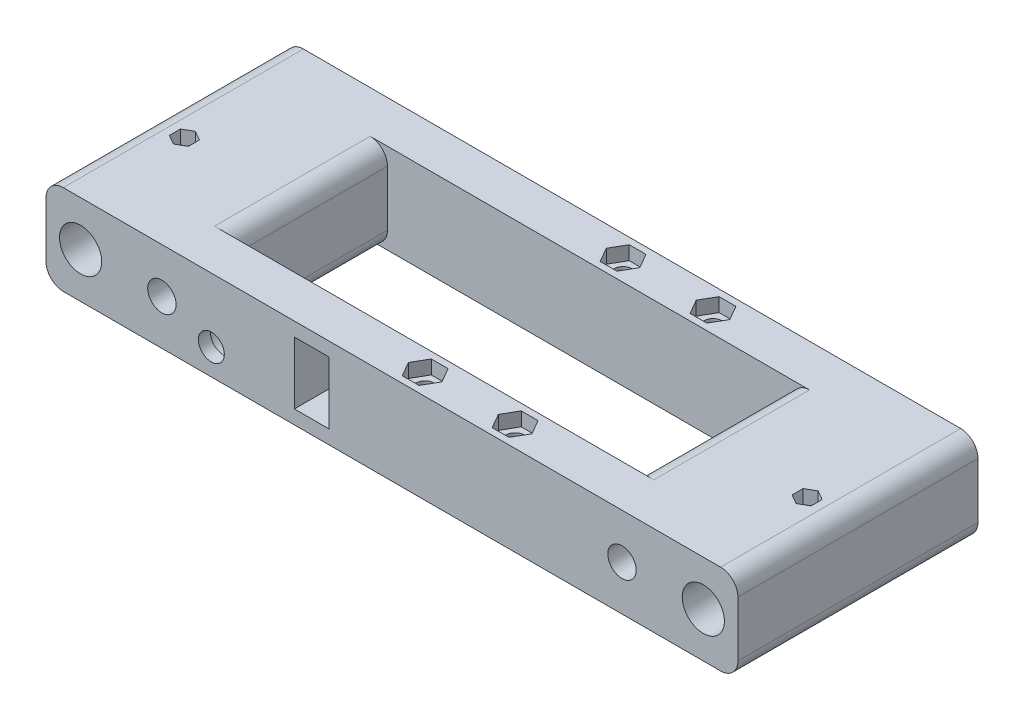
SolidWorks part; units mm, degrees
ref_plane "Front Plane" through (0, 0, 0) normal (0, 0, 1) x (1, 0, 0)
ref_plane "Top Plane" through (0, 0, 0) normal (0, 1, 0) x (1, 0, 0)
ref_plane "Right Plane" through (0, 0, 0) normal (1, 0, 0) x (0, 0, -1)
sketch "Sketch1" plane through (0, 0, 0) normal (0, 0, 1) x (1, 0, 0)
  line L0 (-58.5, 26) -> (-58.5, 0) construction
  line L1 (0, 0) -> (-100, 0)
  line L2 (0, 0) -> (0, 26)
  line L3 (0, 26) -> (-100, 26)
  line L4 (-100, 0) -> (-100, 26)
  circle A0 centre (-90, 13) radius 6.1
  circle A1 centre (-66.5, 13) radius 4.1
  point P9 (-100, 13)
  dimension "D3" = 12.2
  dimension "D4" = 8.2
  dimension "D1" = 100
  dimension "D2" = 26
  dimension "D5" = 23.5
  dimension "D6" = 10
  dimension "D7" = 8
  dimension "D8" = 41.5
extrude "Boss-Extrude1" add sketch "Sketch1" along normal blind 40
sketch "Sketch2" plane through (0, 0, 0) normal (0, 0, -1) x (-1, 0, 0)
  line L1 (100, 26) -> (0, 26)
  line L2 (100, 26) -> (100, 0)
  line L3 (100, 0) -> (0, 0)
  line L4 (0, 26) -> (0, 0)
extrude "Boss-Extrude2" add sketch "Sketch2" along normal blind 29.4
sketch "Sketch3" plane through (0, 26, 0) normal (0, 1, 0) x (1, 0, 0)
  line L0 (0, -40) -> (0, 29.4) construction
  line L1 (0, 17.2) -> (-58.5, 17.2)
  line L2 (0, 17.2) -> (0, -27.8)
  line L3 (0, -27.8) -> (-58.5, -27.8)
  line L4 (-58.5, 17.2) -> (-58.5, -27.8)
  line L5 (-100, -40) -> (-100, 29.4) construction
  line L6 (-100, 29.4) -> (0, 29.4) construction
  line L7 (0, -40) -> (-100, -40) construction
  dimension "D1" = 41.5
  dimension "D2" = 12.2
  dimension "D3" = 12.2
extrude "Cut-Extrude1" cut sketch "Sketch3" against normal up to next
mirror "Mirror2" about plane through (0, 0, 40) normal (-1, 0, 0) of "Boss-Extrude2", "Cut-Extrude1", "Boss-Extrude1"
sketch "Sketch4" plane through (0, 26, 0) normal (0, 1, 0) x (1, 0, 0)
  line L0 (-100, 29.4) -> (100, 29.4) construction
  line L1 (-5.5, 29.4) -> (-5.5, 17.2) construction
  line L2 (58.5, 17.2) -> (-58.5, 17.2) construction
  line L3 (58.5, 17.2) -> (58.5, -27.8) construction
  circle A0 centre (3.5, 23.3) radius 2.6
  circle A1 centre (29.5, 23.3) radius 2.6
  dimension "D1" = 6.1
  dimension "D3" = 9
  dimension "D4" = 26
  dimension "D5" = 5.2
  dimension "D2" = 64
extrude "Cut-Extrude2" cut sketch "Sketch4" against normal through all
sketch "Sketch5" plane through (0, 0, 0) normal (0, -1, 0) x (1, 0, 0)
  line L1 (34.2343, -23.3) -> (31.8671, -19.2)
  line L2 (31.8671, -19.2) -> (27.1329, -19.2)
  line L3 (27.1329, -19.2) -> (24.7657, -23.3)
  line L4 (24.7657, -23.3) -> (27.1329, -27.4)
  line L5 (27.1329, -27.4) -> (31.8671, -27.4)
  line L6 (31.8671, -27.4) -> (34.2343, -23.3)
  line L7 (-1.2343, -23.3) -> (1.1329, -27.4)
  line L8 (1.1329, -27.4) -> (5.8671, -27.4)
  line L9 (5.8671, -27.4) -> (8.2343, -23.3)
  line L10 (8.2343, -23.3) -> (5.8671, -19.2)
  line L11 (5.8671, -19.2) -> (1.1329, -19.2)
  line L12 (1.1329, -19.2) -> (-1.2343, -23.3)
  circle A0 centre (29.5, -23.3) radius 4.1 construction
  circle A1 centre (3.5, -23.3) radius 4.1 construction
  dimension "D1" = 8.2
  dimension "D2" = 8.2
extrude "Cut-Extrude3" cut sketch "Sketch5" against normal blind 4
ref_plane "Plane1" through (0, 0, 5.3) normal (0, 0, 1) x (1, 0, 0)
mirror "Mirror3" about plane through (0, 0, 5.3) normal (0, 0, 1) of "Cut-Extrude3", "Cut-Extrude2"
sketch "Sketch6" plane through (0, 0, 40) normal (0, 0, 1) x (1, 0, 0)
  line L0 (-8.1, 26) -> (-8.1, 0) construction
  line L1 (100, 26) -> (-100, 26) construction
  line L2 (-100, 0) -> (100, 0) construction
  line L3 (0.9, 26) -> (0.9, 4) construction
  line L4 (-100, 26) -> (-100, 0) construction
  line L5 (-18.2, 22) -> (-28.2, 22)
  line L6 (-18.2, 22) -> (-18.2, 4)
  line L7 (-18.2, 4) -> (-28.2, 4)
  line L8 (-28.2, 22) -> (-28.2, 4)
  point P12 (-28.2, 13)
  point P15 (-100, 13)
  dimension "D1" = 9
  dimension "D2" = 10.1
  dimension "D3" = 10
  dimension "D4" = 18
extrude "Cut-Extrude4" cut sketch "Sketch6" against normal up to vertex (14 mm away) up to point (0, -58.5, 26)
fillet "Fillet1" radius 5 8 edges at (58.5, 0, 5.3) (-58.5, 0, 5.3) (58.5, 26, 5.3) (100, 0, 5.3) (100, 26, 5.3) (-100, 0, 5.3) (-100, 26, 5.3) (-58.5, 26, 5.3)
sketch "Sketch7" plane through (0, 26, 0) normal (0, 1, 0) x (1, 0, 0)
  line L0 (63.5, 17.2) -> (-63.5, 17.2) construction
  line L1 (8.3497, 23.3) -> (5.9249, 27.5)
  line L2 (5.9249, 27.5) -> (1.0751, 27.5)
  line L3 (1.0751, 27.5) -> (-1.3497, 23.3)
  line L4 (-1.3497, 23.3) -> (1.0751, 19.1)
  line L5 (1.0751, 19.1) -> (5.9249, 19.1)
  line L6 (5.9249, 19.1) -> (8.3497, 23.3)
  line L7 (34.3497, 23.3) -> (31.9249, 27.5)
  line L8 (31.9249, 27.5) -> (27.0751, 27.5)
  line L9 (27.0751, 27.5) -> (24.6503, 23.3)
  line L10 (24.6503, 23.3) -> (27.0751, 19.1)
  line L11 (27.0751, 19.1) -> (31.9249, 19.1)
  line L12 (31.9249, 19.1) -> (34.3497, 23.3)
  circle A0 centre (3.5, 23.3) radius 4.2 construction
  circle A1 centre (29.5, 23.3) radius 4.2 construction
  point P20 (29.5, 19.1)
  dimension "D1" = 8.4
  dimension "D2" = 8.4
extrude "Cut-Extrude5" cut sketch "Sketch7" against normal blind 4
mirror "Mirror4" about plane through (0, 0, 5.3) normal (0, 0, 1) of "Cut-Extrude5"
sketch "Sketch8" plane through (0, 4, 0) normal (0, -1, 0) x (1, 0, 0)
  line L0 (27.1329, 38) -> (31.8671, 38) construction
  line L1 (31.8671, 38) -> (34.2343, 33.9) construction
  line L2 (34.2343, 33.9) -> (31.8671, 29.8) construction
  line L3 (31.8671, 29.8) -> (27.1329, 29.8) construction
  line L4 (27.1329, 29.8) -> (24.7657, 33.9) construction
  line L5 (24.7657, 33.9) -> (27.1329, 38) construction
  line L6 (1.1329, 38) -> (5.8671, 38) construction
  line L7 (5.8671, 38) -> (8.2343, 33.9) construction
  line L8 (8.2343, 33.9) -> (5.8671, 29.8) construction
  line L9 (5.8671, 29.8) -> (1.1329, 29.8) construction
  line L10 (1.1329, 29.8) -> (-1.2343, 33.9) construction
  line L11 (-1.2343, 33.9) -> (1.1329, 38) construction
  line L12 (27.1329, 38) -> (31.8671, 38)
  line L13 (31.8671, 38) -> (34.2343, 33.9)
  line L14 (34.2343, 33.9) -> (31.8671, 29.8)
  line L15 (31.8671, 29.8) -> (27.1329, 29.8)
  line L16 (27.1329, 29.8) -> (24.7657, 33.9)
  line L17 (24.7657, 33.9) -> (27.1329, 38)
  line L18 (1.1329, 38) -> (5.8671, 38)
  line L19 (5.8671, 38) -> (8.2343, 33.9)
  line L20 (8.2343, 33.9) -> (5.8671, 29.8)
  line L21 (5.8671, 29.8) -> (1.1329, 29.8)
  line L22 (1.1329, 29.8) -> (-1.2343, 33.9)
  line L23 (-1.2343, 33.9) -> (1.1329, 38)
  circle A0 centre (3.5, 33.9) radius 2.6 construction
  circle A1 centre (29.5, 33.9) radius 2.6 construction
  circle A2 centre (3.5, 33.9) radius 2.6
  circle A3 centre (29.5, 33.9) radius 2.6
extrude "Boss-Extrude3" add sketch "Sketch8" along normal up to surface (4 mm away) up to face at (3.5, 0, 33.9)
sketch "Sketch9" plane through (0, 4, 0) normal (0, -1, 0) x (1, 0, 0)
  line L0 (31.8671, -19.2) -> (27.1329, -19.2) construction
  line L1 (34.2343, -23.3) -> (31.8671, -19.2) construction
  line L2 (31.8671, -27.4) -> (34.2343, -23.3) construction
  line L3 (27.1329, -27.4) -> (31.8671, -27.4) construction
  line L4 (24.7657, -23.3) -> (27.1329, -27.4) construction
  line L5 (27.1329, -19.2) -> (24.7657, -23.3) construction
  line L6 (1.1329, -19.2) -> (-1.2343, -23.3) construction
  line L7 (5.8671, -19.2) -> (1.1329, -19.2) construction
  line L8 (8.2343, -23.3) -> (5.8671, -19.2) construction
  line L9 (5.8671, -27.4) -> (8.2343, -23.3) construction
  line L10 (1.1329, -27.4) -> (5.8671, -27.4) construction
  line L11 (-1.2343, -23.3) -> (1.1329, -27.4) construction
  line L12 (31.8671, -19.2) -> (27.1329, -19.2)
  line L13 (34.2343, -23.3) -> (31.8671, -19.2)
  line L14 (31.8671, -27.4) -> (34.2343, -23.3)
  line L15 (27.1329, -27.4) -> (31.8671, -27.4)
  line L16 (24.7657, -23.3) -> (27.1329, -27.4)
  line L17 (27.1329, -19.2) -> (24.7657, -23.3)
  line L18 (1.1329, -19.2) -> (-1.2343, -23.3)
  line L19 (5.8671, -19.2) -> (1.1329, -19.2)
  line L20 (8.2343, -23.3) -> (5.8671, -19.2)
  line L21 (5.8671, -27.4) -> (8.2343, -23.3)
  line L22 (1.1329, -27.4) -> (5.8671, -27.4)
  line L23 (-1.2343, -23.3) -> (1.1329, -27.4)
  circle A0 centre (3.5, -23.3) radius 2.6 construction
  circle A1 centre (29.5, -23.3) radius 2.6 construction
  circle A2 centre (3.5, -23.3) radius 2.6
  circle A3 centre (29.5, -23.3) radius 2.6
extrude "Boss-Extrude4" add sketch "Sketch9" along normal up to surface (4 mm away) up to face at (29.5, 0, -23.3)
sketch "Sketch10" plane through (0, 0, 0) normal (0, -1, 0) x (1, 0, 0)
  line L1 (-96.1, 0) -> (-83.9, 0) construction
  line L2 (83.9, 0) -> (96.1, 0) construction
  circle A0 centre (-90, 10) radius 1.5
  circle A1 centre (90, 10) radius 1.5
  point P5 (-90, 0)
  point P14 (90, 0)
  dimension "D3" = 3
  dimension "D4" = 3
  dimension "D1" = 10
  dimension "D2" = 10
extrude "Cut-Extrude6" cut sketch "Sketch10" against normal through all
sketch "Sketch11" plane through (0, 26, 0) normal (0, 1, 0) x (1, 0, 0)
  line L0 (-95, 29.4) -> (-95, -40) construction
  line L1 (-90, -13.1754) -> (-87.25, -11.5877)
  line L2 (-87.25, -11.5877) -> (-87.25, -8.4123)
  line L3 (-87.25, -8.4123) -> (-90, -6.8246)
  line L4 (-90, -6.8246) -> (-92.75, -8.4123)
  line L5 (-92.75, -8.4123) -> (-92.75, -11.5877)
  line L6 (-92.75, -11.5877) -> (-90, -13.1754)
  line L7 (90, -13.1754) -> (92.75, -11.5877)
  line L8 (92.75, -11.5877) -> (92.75, -8.4123)
  line L9 (92.75, -8.4123) -> (90, -6.8246)
  line L10 (90, -6.8246) -> (87.25, -8.4123)
  line L11 (87.25, -8.4123) -> (87.25, -11.5877)
  line L12 (87.25, -11.5877) -> (90, -13.1754)
  line L13 (95, -40) -> (95, 29.4) construction
  circle A0 centre (-90, -10) radius 2.75 construction
  circle A1 centre (90, -10) radius 2.75 construction
  point P10 (92.75, -10)
  dimension "D1" = 5.5
  dimension "D2" = 5.5
extrude "Cut-Extrude7" cut sketch "Sketch11" against normal blind 4
hole_wizard "Hole1" positions "3DSketch1" profile "Sketch12" legacy end condition through all
sketch3d "3DSketch1"
  line L0 (-58.5, 5, 27.8) -> (-58.5, 21, 27.8) construction
  line L1 (63.5, 0, 27.8) -> (-63.5, 0, 27.8) construction
  point P0 (-52.21, 7.5, 27.8)
  dimension "D1" = 6.29
  dimension "D2" = 7.5
sketch "Sketch12" plane through (-52.21, 7.5, 27.8) normal (1, 0, 0) x (0, 1, 0)
  line L0 (0, 0) -> (0, 12.2)
  line L1 (0, 12.2) -> (3.75, 12.2)
  line L2 (3.75, 12.2) -> (3.75, 8.7)
  line L3 (3.75, 8.7) -> (5.5, 8.7)
  line L4 (5.5, 8.7) -> (5.5, 0)
  line L5 (5.5, 0) -> (0, 0)
  line L6 (0, 110) -> (0, -10) construction
  dimension "Diameter" = 7.5
  dimension "Depth" = 12.2
  dimension "C-Bore Diameter" = 11
  dimension "C-Bore Depth" = 8.7
